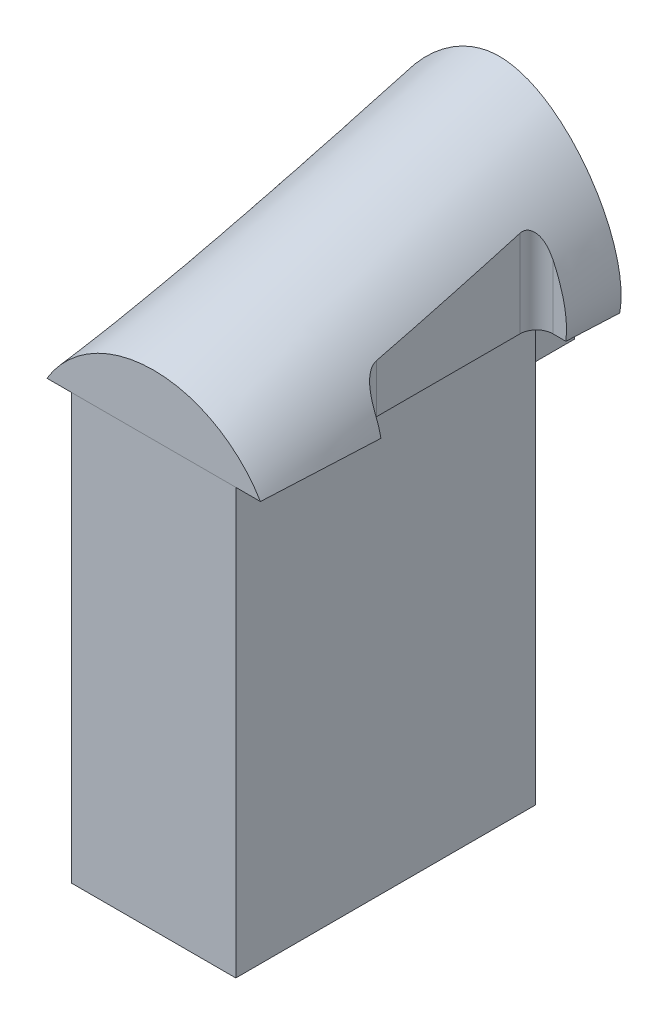
SolidWorks part; units mm, degrees
ref_plane "前视基准面" through (0, 0, 0) normal (0, 0, 1) x (1, 0, 0)
ref_plane "上视基准面" through (0, 0, 0) normal (0, 1, 0) x (1, 0, 0)
ref_plane "右视基准面" through (0, 0, 0) normal (1, 0, 0) x (0, 0, -1)
other "质心 (COM)"
sketch "草图1" plane through (0, 0, 0) normal (0, 1, 0) x (1, 0, 0)
  line L1 (-20, -36.5) -> (20, -36.5)
  line L2 (-20, -36.5) -> (-20, 36.5)
  line L3 (-20, 36.5) -> (20, 36.5)
  line L4 (20, -36.5) -> (20, 36.5)
  line L5 (-20, -36.5) -> (20, 36.5) construction
  line L6 (-20, 36.5) -> (20, -36.5) construction
  point P0 (0, 0)
  dimension "D1" = 40
  dimension "D2" = 73
extrude "凸台-拉伸1" add sketch "草图1" along normal mid plane 103.5
sketch "草图2" plane through (0, 0, -36.5) normal (0, 0, -1) x (-1, 0, 0)
  line L0 (-20, 51.75) -> (-20, -51.75) construction
  line L1 (-19, 51.75) -> (7.5, 51.75)
  line L2 (-19, 51.75) -> (-19, 40.75)
  line L3 (-19, 40.75) -> (7.5, 40.75)
  line L4 (7.5, 51.75) -> (7.5, 40.75)
  dimension "D1" = 11
  dimension "D2" = 26.5
  dimension "D3" = 1
extrude "凸台-拉伸2" add sketch "草图2" along normal blind 10.5
sketch "草图3" plane through (0, 0, -47) normal (0, 0, -1) x (-1, 0, 0)
  line L0 (-30, 51.75) -> (30, 51.75)
  line L2 (-20, -51.75) -> (20, -51.75) construction
  spline S0 degree 3 poles (-30, 51.75) (-32.9608, 67.553) (-0.1223, 116.2579) (33.0721, 64.9367) (30, 51.75) knots 0 0 0 0 0.500505 1 1 1 1
  point P4 (0, 51.75)
  point P12 (-16.8524, 83.8663)
  dimension "D1" = 60
  dimension "D2" = 143
sketch "草图4" plane through (0, 0, 36.5) normal (0, 0, 1) x (1, 0, 0)
  line L0 (-26, 51.75) -> (26, 51.75)
  line L1 (30, 51.75) -> (-30, 51.75) construction
  arc A0 (-26, 51.75) -> (26, 51.75) centre (0, 36.1214) cw
  point P4 (0, 51.75)
  dimension "D1" = 52
loft "放样1" add profiles "草图3", "草图4"
sketch "草图5" plane through (0, 51.75, 0) normal (0, -1, 0) x (1, 0, 0)
  line L0 (0, 13.4118) -> (0, -19.6269) construction
  line L1 (-27.3413, 8.5) -> (-26.243, 8.5)
  line L3 (-22.243, 4.5) -> (-22.243, -30.5)
  line L4 (-26.243, -34.5) -> (-29.4012, -34.5)
  line L5 (-29.4012, -34.5) -> (-36.9893, -34.5)
  line L6 (-26, 36.5) -> (26, 36.5) construction
  line L7 (36.9893, 9.3475) -> (27.3413, 8.5)
  line L8 (36.9893, -34.5) -> (36.9893, 9.3475)
  line L9 (29.4012, -34.5) -> (36.9893, -34.5)
  line L10 (26.243, -34.5) -> (29.4012, -34.5)
  line L12 (-36.9893, -34.5) -> (-36.9893, 9.3475)
  line L13 (-36.9893, 9.3475) -> (-27.3413, 8.5)
  line L14 (22.243, 4.5) -> (22.243, -30.5)
  line L15 (27.3413, 8.5) -> (26.243, 8.5)
  arc A0 (-22.243, -30.5) -> (-26.243, -34.5) centre (-26.243, -30.5) cw
  arc A1 (-22.243, 4.5) -> (-26.243, 8.5) centre (-26.243, 4.5) ccw
  arc A2 (22.243, 4.5) -> (26.243, 8.5) centre (26.243, 4.5) cw
  arc A3 (22.243, -30.5) -> (26.243, -34.5) centre (26.243, -30.5) ccw
  dimension "D3" = 4
  dimension "D1" = 28
  dimension "D2" = 71
extrude "切除-拉伸1" cut sketch "草图5" against normal through all
